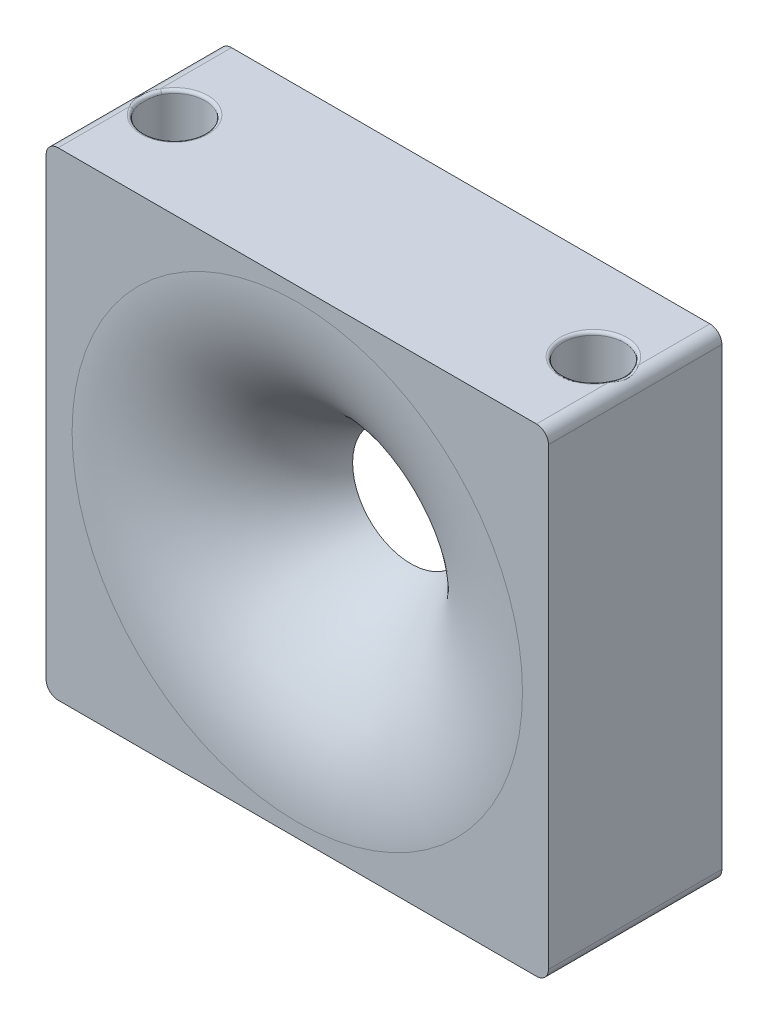
SolidWorks part; units mm, degrees
ref_plane "Front Plane" through (0, 0, 0) normal (1, 0, 0) x (0, 1, 0)
ref_plane "Top Plane" through (0, 0, 0) normal (0, 0, 1) x (0, 1, 0)
ref_plane "Right Plane" through (0, 0, 0) normal (0, 1, 0) x (-1, 0, 0)
sketch "Sketch1" plane through (0, 0, 0) normal (0, 0, 1) x (0, 1, 0)
  line L1 (-40, -42) -> (40, -42)
  line L2 (-40, -42) -> (-40, 42)
  line L3 (-40, 42) -> (40, 42)
  line L4 (40, -42) -> (40, 42)
  line L5 (-40, -42) -> (40, 42) construction
  line L6 (-40, 42) -> (40, -42) construction
  circle A0 centre (0, 0) radius 9.75
  point P0 (0, 0)
  dimension "D3" = 19.5
  dimension "D1" = 84
  dimension "D2" = 80
extrude "29 mm extrude" add sketch "Sketch1" along normal blind 29
sketch "Sketch2" plane through (0, 0, 0) normal (0, 0, -1) x (1, 0, 0)
  circle A0 centre (0, 0) radius 28.5
  dimension "D1" = 57
extrude "7 mm cut" cut sketch "Sketch2" against normal blind 10
fillet "30R funnel slope" radius 30 1 edges at (9.75, 0, 29)
sketch "Sketch3" plane through (0, 40, 0) normal (0, 1, 0) x (-1, 0, 0)
  line L0 (-42, 14.5) -> (42, 14.5) construction
  line L1 (-42, 29) -> (-42, 0) construction
  line L2 (42, 29) -> (42, 0) construction
  line L3 (0, 29) -> (0, 0) construction
  line L4 (-42, 29) -> (42, 29) construction
  line L5 (-42, 14.5) -> (-40.125, 14.5)
  circle A0 centre (-35.025, 14.5) radius 5.1
  circle A1 centre (35.025, 14.5) radius 5.1
  dimension "D1" = 10.2
extrude "36 mm cut screw head" cut sketch "Sketch3" against normal blind 36 contours A0 | A1 region at (35.025, 40, 14.5) region at (-35.025, 40, 14.5)
sketch "Sketch5" plane through (0, 40, 0) normal (0, 1, 0) x (-1, 0, 0)
  circle A0 centre (-35.025, 14.5) radius 3.1
  circle A1 centre (-35.025, 14.5) radius 5.1 construction
  dimension "D1" = 6.2
extrude "7.8mm bore" cut sketch "Sketch5" against normal through all
fillet "3R pig hole" radius 3 1 edges at (-28.5, 0, 10)
fillet "2R corners" radius 2 4 edges at (-42, 40, 14.5) (-42, -40, 14.5) (42, -40, 14.5) (42, 40, 14.5)
fillet "0.5R bolts" radius 0.5 4 edges at (-40.0911, 39.9979, 15.0869) (40.0911, 39.9979, 13.9131) (-29.925, 40, 14.5) (29.925, 40, 14.5)
mirror "Mirror1" about plane through (0, 0, 0) normal (1, 0, 0) of "7.8mm bore"
